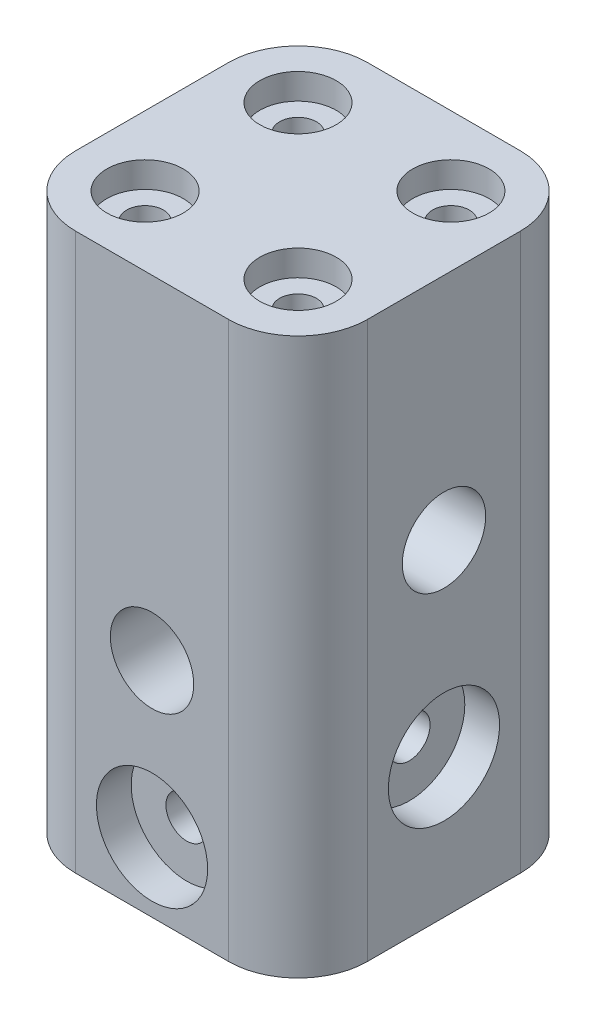
SolidWorks part; units mm, degrees
ref_plane "Front Plane" through (0, 0, 0) normal (0, 0, 1) x (1, 0, 0)
ref_plane "Top Plane" through (0, 0, 0) normal (0, 1, 0) x (1, 0, 0)
ref_plane "Right Plane" through (0, 0, 0) normal (1, 0, 0) x (0, 0, -1)
sketch "Sketch1" plane through (0, 0, 0) normal (0, 1, 0) x (1, 0, 0)
  line L1 (-21, 21) -> (21, 21)
  line L2 (-21, 21) -> (-21, -21)
  line L3 (-21, -21) -> (21, -21)
  line L4 (21, 21) -> (21, -21)
  line L5 (-21, 21) -> (21, -21) construction
  line L6 (-21, -21) -> (21, 21) construction
  point P0 (0, 0)
  dimension "D1" = 42
  dimension "D2" = 42
extrude "Boss-Extrude1" add sketch "Sketch1" along normal blind 80
sketch "Sketch2" plane through (0, 0, 21) normal (0, 0, 1) x (1, 0, 0)
  line L0 (-21, 0) -> (21, 0) construction
  line L1 (0, -1000) -> (0, 49000) construction
  circle A0 centre (0, 32) radius 6
  point P7 (0, 0)
  dimension "D1" = 12
  dimension "D2" = 32
extrude "Cut-Extrude1" cut sketch "Sketch2" against normal through all
sketch "Sketch3" plane through (21, 0, 0) normal (1, 0, 0) x (0, 0, -1)
  line L0 (0, -1000) -> (0, 49000) construction
  circle A0 centre (0, 47) radius 6
  dimension "D1" = 12
  dimension "D2" = 47
extrude "Cut-Extrude2" cut sketch "Sketch3" against normal through all
sketch "Sketch4" plane through (0, 0, 21) normal (0, 0, 1) x (1, 0, 0)
  line L0 (21, 80) -> (21, 0) construction
  line L1 (-21, 0) -> (21, 0) construction
  circle A0 centre (0, 10) radius 3
  dimension "D1" = 6
  dimension "D2" = 10
  dimension "D3" = 21
extrude "Cut-Extrude3" cut sketch "Sketch4" against normal through all
sketch "Sketch5" plane through (0, 0, 21) normal (0, 0, 1) x (1, 0, 0)
  circle A0 centre (0, 10) radius 8
  dimension "D1" = 16
extrude "Cut-Extrude4" cut sketch "Sketch5" against normal blind 5
sketch "Sketch6" plane through (0, 0, -21) normal (0, 0, -1) x (-1, 0, 0)
  circle A0 centre (0, 10) radius 8
  dimension "D1" = 16
extrude "Cut-Extrude5" cut sketch "Sketch6" against normal blind 5
sketch "Sketch7" plane through (21, 0, 0) normal (1, 0, 0) x (0, 0, -1)
  line L0 (0, -1000) -> (0, 49000) construction
  line L1 (-21, 0) -> (21, 0) construction
  circle A0 centre (0, 20) radius 3
  dimension "D1" = 6
  dimension "D2" = 20
extrude "Cut-Extrude6" cut sketch "Sketch7" against normal through all
sketch "Sketch8" plane through (21, 0, 0) normal (1, 0, 0) x (0, 0, -1)
  circle A0 centre (0, 20) radius 8
  dimension "D1" = 16
extrude "Cut-Extrude7" cut sketch "Sketch8" against normal blind 5
sketch "Sketch9" plane through (-21, 0, 0) normal (-1, 0, 0) x (0, 0, 1)
  circle A0 centre (0, 20) radius 8
  dimension "D1" = 16
extrude "Cut-Extrude8" cut sketch "Sketch9" against normal blind 5
fillet "Fillet1" radius 10 4 edges at (21, 40, 21) (21, 40, -21) (-21, 40, 21) (-21, 40, -21)
hole_wizard "CBORE for M5 Pan Head Machine Screw1" positions "Sketch11" profile "Sketch10" counterbore size "M5" standard "ANSI Metric" end condition through all
sketch "Sketch11" plane through (0, 80, 0) normal (0, 1, 0) x (1, 0, 0)
  line L0 (-21, 11) -> (-21, -11) construction
  line L1 (11, 21) -> (-11, 21) construction
  line L2 (21, -11) -> (21, 11) construction
  line L3 (-11, -21) -> (11, -21) construction
  point P0 (-11, 11)
  point P2 (11, 11)
  point P4 (11, -11)
  point P6 (-11, -11)
  dimension "D1" = 10
  dimension "D2" = 10
  dimension "D3" = 10
  dimension "D4" = 10
  dimension "D5" = 10
  dimension "D6" = 10
  dimension "D7" = 10
  dimension "D8" = 10
sketch "Sketch10" plane through (-11, 80, -11) normal (1, 0, 0) x (0, 0, 1)
  line L0 (0, 0) -> (0, 80)
  line L1 (0, 80) -> (2.65, 80)
  line L3 (2.65, 80) -> (2.65, 3.7)
  line L4 (2.65, 3.7) -> (5.5, 3.7)
  line L5 (5.5, 3.7) -> (5.5, 0)
  line L7 (5.5, 0) -> (0, 0)
  line L11 (0, -6.35) -> (0, 107.95) construction
  dimension "Thru Hole Dia." = 5.3
  dimension "Thru Hole Depth" = 80
  dimension "C'Bore Dia." = 11
  dimension "C'Bore Depth" = 3.7
